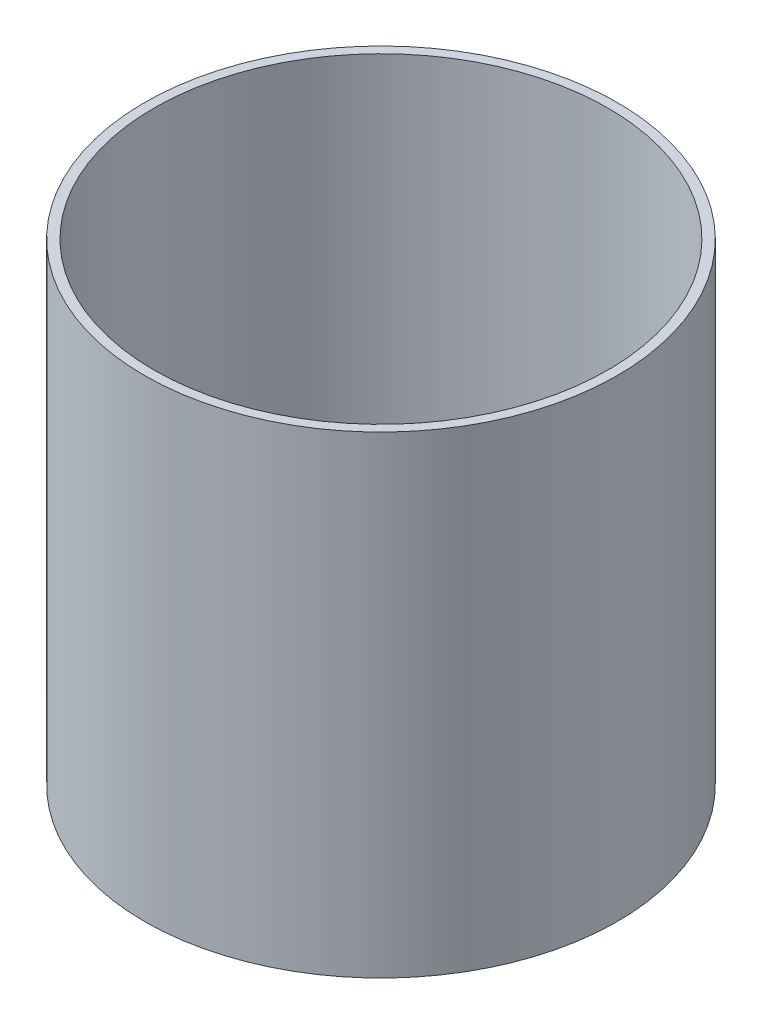
SolidWorks part; units mm, degrees
ref_plane "Front Plane" through (0, 0, 0) normal (0, 0, 1) x (1, 0, 0)
ref_plane "Top Plane" through (0, 0, 0) normal (0, 1, 0) x (1, 0, 0)
ref_plane "Right Plane" through (0, 0, 0) normal (1, 0, 0) x (0, 0, -1)
sketch "Sketch1" plane through (0, 0, 0) normal (0, 1, 0) x (1, 0, 0)
  circle A0 centre (0, 0) radius 1250
  circle A1 centre (0, 0) radius 1200
  circle A2 centre (0, 0) radius 1225 construction
  dimension "D1" = 2400
  dimension "D2" = 2500
  dimension "D3" = 2450
extrude "Boss-Extrude1" add sketch "Sketch1" along normal blind 2500
